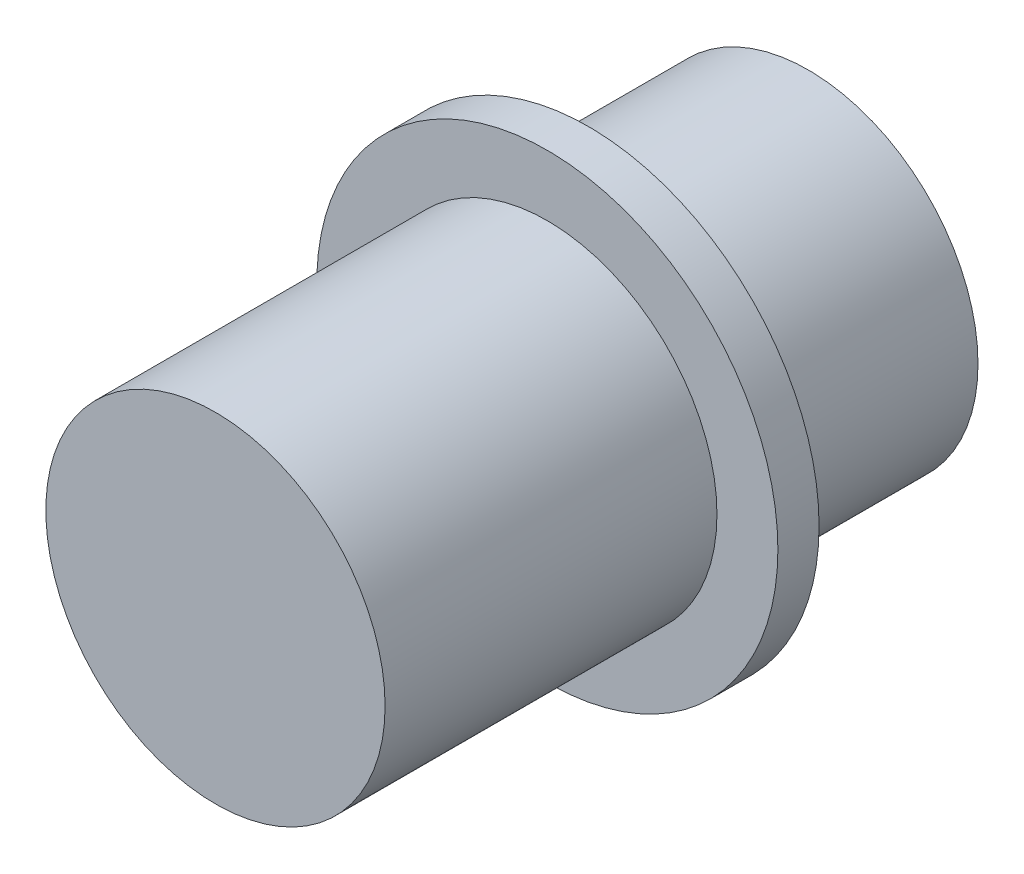
SolidWorks part; units mm, degrees
ref_plane "Front Plane" through (0, 0, 0) normal (0, 0, 1) x (1, 0, 0)
ref_plane "Top Plane" through (0, 0, 0) normal (0, 1, 0) x (1, 0, 0)
ref_plane "Right Plane" through (0, 0, 0) normal (1, 0, 0) x (0, 0, -1)
sketch "Sketch1" plane through (0, 0, 0) normal (0, 0, 1) x (1, 0, 0)
  circle A0 centre (0, 0) radius 10.3
  circle A1 centre (0, 0) radius 14
  dimension "D1" = 20.6
  dimension "D2" = 28
extrude "Boss-Extrude1" add sketch "Sketch1" along normal blind 20.15 contours A0 region at (0, 0, 0)
extrude "Boss-Extrude2" add sketch "Sketch1<3>" against normal blind 2.5 contours A0 | A1 A0 region at (0, 0, 0) region at (-13.604, 0, 0)
sketch "Sketch1<3>" plane through (0, 0, 0) normal (0, 0, 1) x (1, 0, 0) same geometry as "Sketch1"
extrude "Boss-Extrude3" add sketch "Sketch1<4>" against normal blind 15.85 contours A0 region at (0, 0, 0)
sketch "Sketch1<4>" plane through (0, 0, 0) normal (0, 0, 1) x (1, 0, 0) same geometry as "Sketch1"
